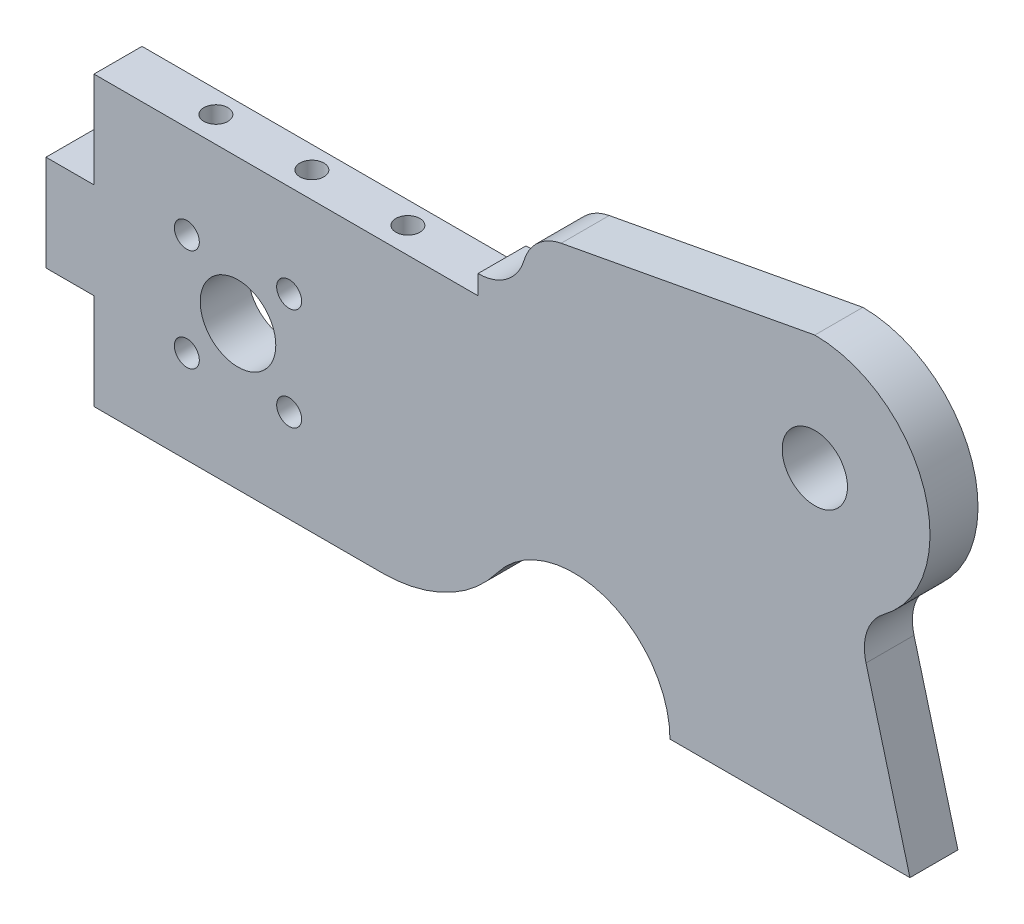
SolidWorks part; units mm, degrees
ref_plane "Front Plane" through (0, 0, 0) normal (0, 0, 1) x (1, 0, 0)
ref_plane "Top Plane" through (0, 0, 0) normal (0, 1, 0) x (1, 0, 0)
ref_plane "Right Plane" through (0, 0, 0) normal (1, 0, 0) x (0, 0, -1)
sketch "Sketch1" plane through (0, 0, 0) normal (0, 0, 1) x (1, 0, 0)
  line L0 (0, 0) -> (107.95, 0)
  line L3 (0, 38.1) -> (0, 25.4)
  line L4 (95.3675, 55.88) -> (0, 38.1)
  line L5 (0, 19.05) -> (100.2273, 19.05) construction
  line L6 (19.05, 19.05) -> (19.05, 28.62) construction
  line L7 (19.05, 19.05) -> (25.817, 25.817) construction
  line L8 (107.95, 0) -> (100.9363, 26.1756)
  line L10 (0, 12.7) -> (0, 0)
  line L11 (0, 25.4) -> (-6.35, 25.4)
  line L13 (0, 12.7) -> (-6.35, 12.7)
  line L14 (-6.35, 25.4) -> (-6.35, 12.7)
  line L15 (100.9363, 26.1756) -> (100.8688, 26.4276)
  arc A0 (100.8688, 26.4276) -> (95.3675, 55.88) centre (95.3675, 40.64) ccw
  circle A1 centre (95.3675, 40.64) radius 4.318
  circle A2 centre (19.05, 19.05) radius 9.57 construction
  circle A3 centre (25.817, 25.817) radius 1.651
  circle A4 centre (25.817, 12.283) radius 1.651
  circle A5 centre (12.283, 12.283) radius 1.651
  circle A6 centre (12.283, 25.817) radius 1.651
  point P26 (19.05, 19.05)
  dimension "D1" = 8.636
  dimension "D5" = 15.24
  dimension "D4" = 19.14
  dimension "D7" = 3.302
  dimension "D11" = 97.0107
  dimension "D2" = 38.1
  dimension "D3" = 40.64
  dimension "D6" = 107.95
  dimension "D8" = 45
  dimension "D9" = 4
  dimension "D10" = 19.05
  dimension "D12" = 75
  dimension "D14" = 12.7
  dimension "D15" = 12.7
  dimension "D16" = 6.35
extrude "Boss-Extrude1" add sketch "Sketch1" along normal blind 6.35
sketch "Sketch2" plane through (0, 0, 6.35) normal (0, 0, 1) x (1, 0, 0)
  circle A0 centre (95.3675, 40.64) radius 38.1 construction
sketch "Sketch3" plane through (0, 0, 0) normal (-1, 0, 0) x (0, 0, 1)
  line L0 (0, 38.1) -> (6.35, 25.4) construction
  line L1 (6.35, 12.7) -> (0, 0) construction
  circle A0 centre (3.175, 31.75) radius 1.5875
  circle A1 centre (3.175, 6.35) radius 1.5875
  dimension "D1" = 3.175
  dimension "D2" = 3.175
extrude "Cut-Extrude1" cut sketch "Sketch3" against normal blind 6.35
sketch "Sketch6" plane through (0, 0, 6.35) normal (0, 0, 1) x (1, 0, 0)
  line L0 (0, 0) -> (107.95, 0) construction
  line L1 (50.8, 0) -> (76.2, 0)
  arc A0 (76.2, 0) -> (50.8, 0) centre (63.5, 0) ccw
  dimension "D1" = 25.4
  dimension "D2" = 31.75
extrude "Cut-Extrude2" cut sketch "Sketch6" against normal blind 6.35
sketch "Sketch7" plane through (0, 0, 6.35) normal (0, 0, 1) x (1, 0, 0)
  line L0 (12.283, 25.817) -> (25.817, 12.283) construction
  line L1 (12.283, 12.283) -> (25.817, 25.817) construction
  circle A0 centre (19.05, 19.05) radius 5
  dimension "D1" = 10
extrude "Cut-Extrude3" cut sketch "Sketch7" against normal through all
fillet "Fillet1" radius 6.35 1 edges at (100.8688, 26.4276, 3.175)
sketch "Sketch8" plane through (0, 0, 6.35) normal (0, 0, 1) x (1, 0, 0)
  line L1 (0, 38.1) -> (50.8, 38.1)
  line L2 (0, 38.1) -> (0, 50.8)
  line L3 (0, 50.8) -> (50.8, 50.8)
  line L4 (50.8, 38.1) -> (50.8, 50.8)
  dimension "D1" = 50.8
  dimension "D2" = 12.7
extrude "Cut-Extrude4" cut sketch "Sketch8" against normal blind 50.8
sketch "Sketch9" plane through (0, 0, 6.35) normal (0, 0, 1) x (1, 0, 0)
  line L3 (50.8, 40.64) -> (57.15, 40.64)
  line L5 (57.15, 40.64) -> (50.8, 40.64)
  line L6 (57.15, 40.64) -> (57.15, 50.8)
  line L7 (57.15, 50.8) -> (50.8, 50.8)
  line L8 (50.8, 40.64) -> (50.8, 50.8)
  line L9 (0, 38.1) -> (50.8, 38.1) construction
  line M8 (50.8, 47.571) -> (50.8, 38.1)
  line M21 (95.3675, 55.88) -> (50.8, 47.571)
  dimension "D1" = 10.16
  dimension "D2" = 2.54
  dimension "D3" = 6.35
extrude "Cut-Extrude5" cut sketch "Sketch9" against normal blind 19.304 contours L3 L6 M21 M8 region at (54.0583, 44.4092, 6.35)
fillet "Fillet6" radius 6.35 1 edges at (57.15, 40.64, 3.175)
fillet "Fillet7" radius 6.35 1 edges at (57.15, 48.7549, 3.175)
fillet "Fillet8" radius 19.05 1 edges at (50.8, 0, 3.175)
sketch "Sketch10" plane through (0, 0, 0) normal (0, -1, 0) x (1, 0, 0)
  line L0 (76.2, 6.35) -> (107.95, 6.35) construction
  line L1 (0, 6.35) -> (0, 0) construction
  line L2 (0, 6.35) -> (38.1, 6.35) construction
  line L3 (107.95, 6.35) -> (107.95, 0) construction
  line L4 (76.2, 0) -> (76.2, 6.35) construction
  circle A0 centre (97.79, 3.175) radius 1.5875
  circle A1 centre (86.36, 3.175) radius 1.5875
  circle A2 centre (31.75, 3.175) radius 1.5875
  circle A3 centre (12.7, 3.175) radius 1.5875
  dimension "D1" = 3.175
  dimension "D2" = 3.175
  dimension "D3" = 3.175
  dimension "D4" = 3.175
  dimension "D5" = 12.7
  dimension "D6" = 19.05
  dimension "D7" = 10.16
  dimension "D8" = 10.16
  dimension "D9" = 11.43
  dimension "D10" = 3.175
  dimension "D11" = 3.175
extrude "Cut-Extrude6" cut sketch "Sketch10" against normal blind 6.35
sketch "Sketch11" plane through (0, 38.1, 0) normal (0, 1, 0) x (1, 0, 0)
  line L0 (0, -6.35) -> (0, 0) construction
  line L1 (50.8, 0) -> (50.8, -6.35) construction
  line L2 (0, -6.35) -> (50.8, -6.35) construction
  circle A0 centre (12.7, -2.9224) radius 1.5875
  circle A1 centre (25.4, -2.9224) radius 1.5875
  circle A2 centre (38.1, -2.9224) radius 1.5875
  dimension "D1" = 3.175
  dimension "D2" = 3.175
  dimension "D3" = 3.175
  dimension "D4" = 12.7
  dimension "D5" = 12.7
  dimension "D6" = 12.7
  dimension "D7" = 12.7
  dimension "D8" = 3.4276
extrude "Cut-Extrude7" cut sketch "Sketch11" against normal blind 6.35
